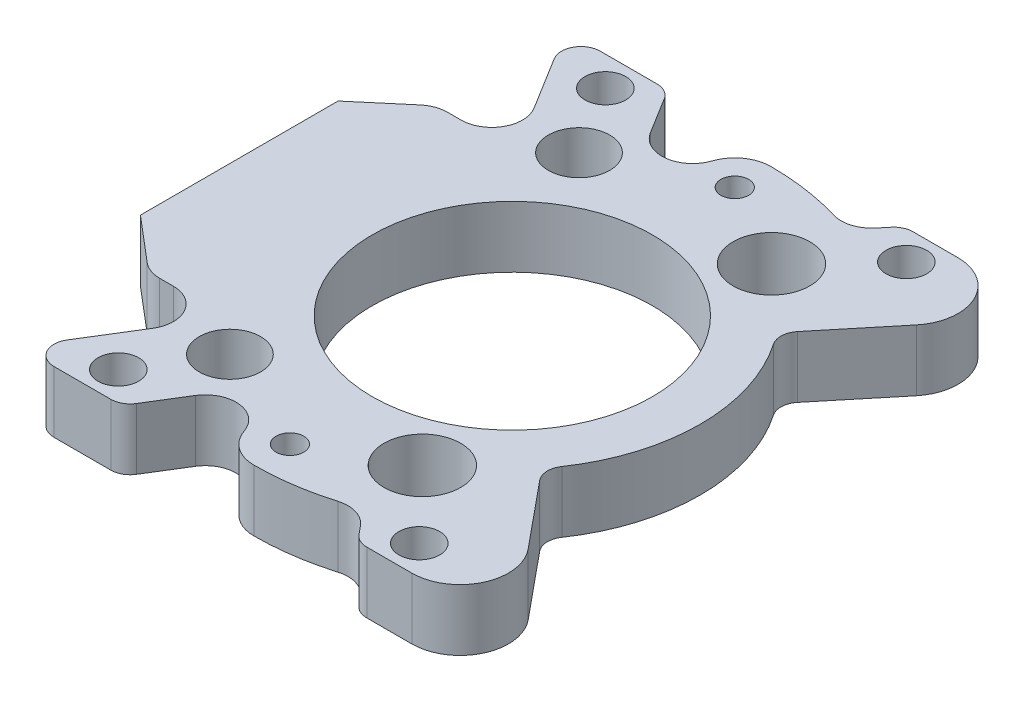
SolidWorks part; units mm, degrees
ref_plane "Front Plane" through (0, 0, 0) normal (0, 0, 1) x (1, 0, 0)
ref_plane "Top Plane" through (0, 0, 0) normal (0, 1, 0) x (1, 0, 0)
ref_plane "Right Plane" through (0, 0, 0) normal (1, 0, 0) x (0, 0, -1)
sketch "Sketch1" plane through (0, 0, 0) normal (0, 1, 0) x (1, 0, 0)
  line L0 (0, 56.515) -> (56.515, 0) construction
  line L1 (0, 0) -> (56.515, 0)
  line L2 (0, 0) -> (0, 56.515)
  line L3 (0, 56.515) -> (56.515, 56.515)
  line L4 (56.515, 0) -> (56.515, 56.515)
  line L6 (12.6873, 3.0607) -> (43.8277, 3.0607) construction
  line L7 (12.6873, 3.0607) -> (12.6873, 53.4543) construction
  line L8 (12.6873, 53.4543) -> (43.8277, 53.4543) construction
  line L9 (43.8277, 3.0607) -> (43.8277, 53.4543) construction
  line L10 (12.6873, 3.0607) -> (43.8277, 53.4543) construction
  line L11 (12.6873, 53.4543) -> (43.8277, 3.0607) construction
  circle A0 centre (43.8277, 3.0607) radius 2.1082
  circle A1 centre (12.6873, 3.0607) radius 2.1082
  circle A2 centre (12.6873, 53.4543) radius 2.1082
  circle A3 centre (43.8277, 53.4543) radius 2.1082
  circle A4 centre (28.2575, 28.2575) radius 14.5
  point P5 (28.2575, 28.2575)
  point P6 (28.2575, 28.2575)
  dimension "D5" = 4.2164
  dimension "D6" = 29
  dimension "D1" = 56.515
  dimension "D2" = 56.515
  dimension "D3" = 31.1404
  dimension "D4" = 50.3936
extrude "Boss-Extrude1" add sketch "Sketch1" along normal blind 6.35
sketch "Sketch3" plane through (0, 6.35, 0) normal (0, 1, 0) x (1, 0, 0)
  line L0 (51.5305, 0) -> (38.0741, 16.3385) construction
  line L1 (37.1401, 4.8887) -> (41.1665, 0) construction
  line L2 (0, 0) -> (56.515, 0) construction
  line L3 (43.8277, 3.0607) -> (-7.9833, 65.9682) construction
  line L4 (51.5305, 0) -> (41.1665, 0) construction
  line L5 (0, 18.6883) -> (7.198, 12.5871) construction
  line L6 (0.2175, 18.5039) -> (5.6815, 13.8725) construction
  line L7 (0, 56.515) -> (0, 0) construction
  line L8 (5.6815, 13.8725) -> (22.645, 13.8725) construction
  line L9 (22.645, 13.8725) -> (25.7282, 2.1296) construction
  line L10 (25.1261, 4.4228) -> (22.645, 13.8725) construction
  line L11 (23.0701, 12.2536) -> (15.4981, 0) construction
  line L12 (14.6663, 13.8725) -> (6.0939, 0) construction
  line L13 (12.6873, 3.0607) -> (50.1607, 63.7028) construction
  line L14 (5.6815, 13.8725) -> (22.645, 13.8725) construction
  line L15 (41.1665, 0) -> (37.9766, 3.8731)
  line L16 (23.0701, 12.2536) -> (25.1261, 4.4228)
  line L17 (23.0701, 12.2536) -> (15.4981, 0)
  line L18 (40.9306, -0.5) -> (37.821, 3.2755) construction
  line L19 (22.8825, 10.9989) -> (24.6425, 4.2958) construction
  line L20 (40.5187, 0) -> (39.2133, 1.585)
  line L21 (51.5305, 0) -> (38.0741, 16.3385) construction
  line L22 (19.0019, 4.7189) -> (16.0858, 0)
  line L23 (40.5187, 0) -> (16.0858, 0)
  line L24 (6.0939, 0) -> (14.6663, 13.8725)
  line L25 (14.6663, 13.8725) -> (5.6815, 13.8725)
  line L26 (5.6815, 13.8725) -> (0, 18.6883)
  line L27 (5.6685, 0.2628) -> (10.7762, 8.5285)
  line L28 (8.0753, 13.3725) -> (6.6627, 13.3725)
  line L29 (4.6098, 14.1255) -> (0, 18.0328)
  line L30 (5.6685, 0.2628) -> (13.7696, 13.3725) construction
  line L31 (13.7696, 13.3725) -> (5.4982, 13.3725) construction
  line L32 (5.4982, 13.3725) -> (-0.3233, 18.3068) construction
  line L33 (0, 0) -> (0, 18.0328)
  line L34 (0, 0) -> (5.5061, 0)
  line L35 (5.6685, 0.2628) -> (5.5061, 0)
  line L36 (22.8825, 10.9989) -> (15.9234, -0.2628) construction
  line L37 (52.5901, -0.5) -> (38.46, 16.6563) construction
  line L38 (52.5901, -0.5) -> (40.9306, -0.5) construction
  line L39 (56.515, 28.2575) -> (28.2575, 28.2575) construction
  line L40 (56.515, 0) -> (56.515, 56.515) construction
  line L41 (51.5305, 56.515) -> (38.0741, 40.1765) construction
  line L42 (54.6181, 53.972) -> (44.4315, 41.6037)
  line L43 (54.6181, 2.543) -> (44.4315, 14.9113)
  line L44 (54.6181, 53.972) -> (43.4402, 40.4001) construction
  line L45 (54.6181, 2.543) -> (43.4402, 16.1149) construction
  line L48 (56.515, 56.515) -> (0, 56.515) construction
  line L50 (56.515, 56.515) -> (56.515, 0)
  line L52 (0, 56.515) -> (5.5061, 56.515)
  line L53 (5.6685, 56.2522) -> (5.5061, 56.515)
  line L54 (5.6685, 56.2522) -> (10.7762, 47.9865)
  line L55 (8.0753, 43.1425) -> (6.6627, 43.1425)
  line L56 (4.6098, 42.3895) -> (0, 38.4822)
  line L57 (0, 56.515) -> (0, 38.4822)
  line L58 (40.5187, 56.515) -> (16.0858, 56.515)
  line L59 (40.5187, 56.515) -> (39.2133, 54.93)
  line L60 (19.0019, 51.7961) -> (16.0858, 56.515)
  line L61 (37.0084, 10.1975) -> (8.0753, 10.1975) construction
  line L62 (33.87, 13.8725) -> (31.3889, 4.4228) construction
  circle A0 centre (28.2575, 51.27) radius 1.435
  circle A1 centre (28.2575, 5.245) radius 1.435
  arc A2 (33.87, 13.8725) -> (33.87, 42.6425) centre (28.2575, 28.2575) ccw construction
  circle A3 centre (28.2575, 28.2575) radius 14.5 construction
  circle A4 centre (28.2575, 28.2575) radius 25 construction
  circle A5 centre (28.2575, 28.2575) radius 26.25 construction
  arc A6 (25.1261, 4.4228) -> (31.3889, 4.4228) centre (28.2575, 5.245) ccw construction
  arc A7 (7.198, 12.5871) -> (37.9766, 3.8731) centre (28.2575, 28.2575) ccw construction
  circle A8 centre (28.2575, 28.2575) radius 14.5 construction
  circle A9 centre (28.2575, 5.245) radius 1.435 construction
  circle A10 centre (28.2575, 51.27) radius 1.435 construction
  arc A11 (37.9766, 3.8731) -> (28.2575, 2.0075) centre (28.2575, 28.2575) cw
  arc A12 (25.1261, 4.4228) -> (28.2575, 2.0075) centre (28.2575, 5.245) ccw
  arc A13 (35.8601, 2.6106) -> (28.2575, 1.5075) centre (28.2575, 28.2575) cw
  arc A14 (24.7134, 4.0582) -> (28.2575, 1.5075) centre (28.2575, 5.245) ccw
  arc A15 (37.821, 3.2755) -> (28.2575, 1.5075) centre (28.2575, 28.2575) cw construction
  arc A16 (10.7762, 8.5285) -> (8.0753, 13.3725) centre (8.0753, 10.1975) ccw
  arc A17 (4.6098, 14.1255) -> (6.6627, 13.3725) centre (6.6627, 16.5475) ccw
  arc A18 (39.2133, 1.585) -> (35.8601, 2.6106) centre (36.7625, -0.4334) ccw
  arc A19 (24.7134, 4.0582) -> (19.0019, 4.7189) centre (21.7028, 3.0499) ccw
  arc A20 (38.0741, 40.1765) -> (38.0741, 16.3385) centre (28.2575, 28.2575) cw
  arc A21 (24.6425, 4.2958) -> (28.2575, 1.5075) centre (28.2575, 5.245) ccw construction
  arc A22 (44.3226, 39.2059) -> (44.3226, 17.3091) centre (28.2575, 28.2575) cw
  arc A23 (43.4402, 40.4001) -> (43.4402, 16.1149) centre (28.2575, 28.2575) cw construction
  arc A24 (44.3226, 39.2059) -> (44.4315, 41.6037) centre (45.9753, 40.3323) cw
  arc A25 (44.4315, 14.9113) -> (44.3226, 17.3091) centre (45.9753, 16.1827) cw
  arc A26 (10.7762, 47.9865) -> (8.0753, 43.1425) centre (8.0753, 46.3175) cw
  arc A27 (4.6098, 42.3895) -> (6.6627, 43.1425) centre (6.6627, 39.9675) cw
  arc A28 (39.2133, 54.93) -> (35.8601, 53.9044) centre (36.7625, 56.9484) cw
  arc A29 (35.8601, 53.9044) -> (28.2575, 55.0075) centre (28.2575, 28.2575) ccw
  arc A30 (24.7134, 52.4568) -> (28.2575, 55.0075) centre (28.2575, 51.27) cw
  arc A31 (24.7134, 52.4568) -> (19.0019, 51.7961) centre (21.7028, 53.4651) cw
  circle A32 centre (37.0084, 10.1975) radius 3.9687
  circle A33 centre (17.0974, 10.1975) radius 3.175
  circle A34 centre (17.0974, 46.3175) radius 3.175
  circle A35 centre (37.0084, 46.3175) radius 3.9688
  arc A36 (46.117, 0) -> (49.9765, 8.1787) centre (46.117, 5) ccw
  arc A38 (46.117, 56.515) -> (49.9765, 48.3363) centre (46.117, 51.515) cw
  point P60 (18.0224, 4.0851)
  point P84 (36.3745, 41.393)
  point P113 (0, 0)
  point P114 (50.6977, 49.2119)
  point P115 (56.0653, 55.7291)
  point P121 (57.9114, -1.4557)
  line M1 (0, 56.515) -> (0, 0)
  line M2 (0, 0) -> (56.515, 0)
  line M3 (56.515, 0) -> (56.515, 56.515)
  line M4 (56.515, 56.515) -> (0, 56.515)
  dimension "D1" = 50
  dimension "D4" = 29
  dimension "D11" = 3.175
  dimension "D12" = 3.175
  dimension "D8" = 3.175
  dimension "D9" = 3.175
  dimension "D14" = 2
  dimension "D15" = 2
  dimension "D16" = 7.9375
  dimension "D17" = 6.35
  dimension "D19" = 5
  dimension "D2" = 8
  dimension "D3" = 4
  dimension "D5" = 8
  dimension "D6" = 4
  dimension "D10" = 0.5
  dimension "D7" = 0.5
  dimension "D13" = 4
extrude "Cut-Extrude1" cut sketch "Sketch3" against normal through all contours A25 L43 L42 A24 A22 M2 M3 M4 | A14 A19 L22 L20 A18 A13 M2 | A17 L29 L35 L27 A16 L28 M1 M2 | L56 A27 L55 A26 L54 L53 M4 M1 | A31 A30 A29 A28 L59 L60 M4 | A33 | A32 | A35 | A34 | A0 | A1 region at (26.1526, 6.35, -1.9586) region at (51.7924, 6.35, -28.2575) region at (4.445, 6.35, -8.0938) region at (26.1526, 6.35, -54.5564) region at (4.445, 6.35, -48.4212) region at (28.2575, 6.35, -51.27) region at (28.2575, 6.35, -5.245) region at (37.0084, 6.35, -10.1975) region at (17.0974, 6.35, -10.1975) region at (17.0974, 6.35, -46.3175) region at (37.0084, 6.35, -46.3175)
fillet "Fillet1" radius 2 6 edges at (5.5061, 3.175, 0) (5.5061, 3.175, -56.515) (40.5187, 3.175, 0) (16.0858, 3.175, 0) (16.0858, 3.175, -56.515) (40.5187, 3.175, -56.515)
sketch "Sketch4" plane through (0, 6.35, 0) normal (0, 1, 0) x (1, 0, 0)
  line L17 (39.2133, 1.585) -> (39.9187, 0.7285)
  line L18 (41.4625, 0) -> (46.117, 0)
  line L19 (49.9765, 8.1787) -> (44.4315, 14.9113)
  line L20 (44.4315, 41.6037) -> (49.9765, 48.3363)
  line L21 (46.117, 56.515) -> (41.4625, 56.515)
  line L22 (39.9187, 55.7865) -> (39.2133, 54.93)
  line L23 (19.0019, 51.7961) -> (16.672, 55.5664)
  line L24 (14.9707, 56.515) -> (9.093, 56.515)
  line L25 (7.3917, 53.4636) -> (10.7762, 47.9865)
  line L26 (8.0753, 43.1425) -> (6.6627, 43.1425)
  line L27 (4.6098, 42.3895) -> (0, 38.4822)
  line L28 (0, 38.4822) -> (0, 18.0328)
  line L29 (0, 18.0328) -> (4.6098, 14.1255)
  line L30 (6.6627, 13.3725) -> (8.0753, 13.3725)
  line L31 (10.7762, 8.5285) -> (7.3917, 3.0514)
  line L32 (9.093, 0) -> (14.9707, 0)
  line L33 (16.672, 0.9486) -> (19.0019, 4.7189)
  line L34 (39.2133, 1.585) -> (39.9187, 0.7285) construction
  line L35 (41.4625, 0) -> (46.117, 0) construction
  line L36 (49.9765, 8.1787) -> (44.4315, 14.9113) construction
  line L37 (44.4315, 41.6037) -> (49.9765, 48.3363) construction
  line L38 (46.117, 56.515) -> (41.4625, 56.515) construction
  line L39 (39.9187, 55.7865) -> (39.2133, 54.93) construction
  line L40 (19.0019, 51.7961) -> (16.672, 55.5664) construction
  line L41 (14.9707, 56.515) -> (9.093, 56.515) construction
  line L42 (7.3917, 53.4636) -> (10.7762, 47.9865) construction
  line L43 (8.0753, 43.1425) -> (6.6627, 43.1425) construction
  line L44 (4.6098, 42.3895) -> (0, 38.4822) construction
  line L45 (0, 38.4822) -> (0, 18.0328) construction
  line L46 (0, 18.0328) -> (4.6098, 14.1255) construction
  line L47 (6.6627, 13.3725) -> (8.0753, 13.3725) construction
  line L48 (10.7762, 8.5285) -> (7.3917, 3.0514) construction
  line L49 (9.093, 0) -> (14.9707, 0) construction
  line L50 (16.672, 0.9486) -> (19.0019, 4.7189) construction
  circle A0 centre (12.6873, 53.4543) radius 2.1082 construction
  circle A1 centre (12.6873, 3.0607) radius 2.1082 construction
  circle A2 centre (43.8277, 3.0607) radius 2.1082 construction
  circle A3 centre (43.8277, 53.4543) radius 2.1082 construction
  circle A4 centre (12.6873, 53.4543) radius 2.1082 construction
  circle A5 centre (12.6873, 3.0607) radius 2.1082 construction
  circle A6 centre (43.8277, 3.0607) radius 2.1082 construction
  circle A7 centre (43.8277, 53.4543) radius 2.1082 construction
  circle A8 centre (43.8277, 53.4543) radius 3.625 construction
  circle A9 centre (12.6873, 53.4543) radius 3.625 construction
  circle A10 centre (43.8277, 3.0607) radius 3.625 construction
  circle A11 centre (12.6873, 3.0607) radius 3.625 construction
  arc A35 (39.9187, 0.7285) -> (41.4625, 0) centre (41.4625, 2) ccw
  arc A36 (46.117, 0) -> (49.9765, 8.1787) centre (46.117, 5) ccw
  arc A37 (44.3226, 17.3091) -> (44.4315, 14.9113) centre (45.9753, 16.1827) ccw
  arc A38 (44.3226, 17.3091) -> (44.3226, 39.2059) centre (28.2575, 28.2575) ccw
  arc A39 (44.4315, 41.6037) -> (44.3226, 39.2059) centre (45.9753, 40.3323) ccw
  arc A40 (49.9765, 48.3363) -> (46.117, 56.515) centre (46.117, 51.515) ccw
  arc A41 (41.4625, 56.515) -> (39.9187, 55.7865) centre (41.4625, 54.515) ccw
  arc A42 (35.8601, 53.9044) -> (39.2133, 54.93) centre (36.7625, 56.9484) ccw
  arc A43 (35.8601, 53.9044) -> (28.2575, 55.0075) centre (28.2575, 28.2575) ccw
  arc A44 (28.2575, 55.0075) -> (24.7134, 52.4568) centre (28.2575, 51.27) ccw
  arc A45 (19.0019, 51.7961) -> (24.7134, 52.4568) centre (21.7028, 53.4651) ccw
  arc A46 (16.672, 55.5664) -> (14.9707, 56.515) centre (14.9707, 54.515) ccw
  arc A47 (9.093, 56.515) -> (7.3917, 53.4636) centre (9.093, 54.515) ccw
  arc A48 (8.0753, 43.1425) -> (10.7762, 47.9865) centre (8.0753, 46.3175) ccw
  arc A49 (6.6627, 43.1425) -> (4.6098, 42.3895) centre (6.6627, 39.9675) ccw
  arc A50 (4.6098, 14.1255) -> (6.6627, 13.3725) centre (6.6627, 16.5475) ccw
  arc A51 (10.7762, 8.5285) -> (8.0753, 13.3725) centre (8.0753, 10.1975) ccw
  arc A52 (7.3917, 3.0514) -> (9.093, 0) centre (9.093, 2) ccw
  arc A53 (14.9707, 0) -> (16.672, 0.9486) centre (14.9707, 2) ccw
  arc A54 (24.7134, 4.0582) -> (19.0019, 4.7189) centre (21.7028, 3.0499) ccw
  arc A55 (24.7134, 4.0582) -> (28.2575, 1.5075) centre (28.2575, 5.245) ccw
  arc A56 (28.2575, 1.5075) -> (35.8601, 2.6106) centre (28.2575, 28.2575) ccw
  arc A57 (39.2133, 1.585) -> (35.8601, 2.6106) centre (36.7625, -0.4334) ccw
  arc A58 (39.9187, 0.7285) -> (41.4625, 0) centre (41.4625, 2) ccw construction
  arc A59 (46.117, 0) -> (49.9765, 8.1787) centre (46.117, 5) ccw construction
  arc A60 (44.3226, 17.3091) -> (44.4315, 14.9113) centre (45.9753, 16.1827) ccw construction
  arc A61 (44.3226, 17.3091) -> (44.3226, 39.2059) centre (28.2575, 28.2575) ccw construction
  arc A62 (44.4315, 41.6037) -> (44.3226, 39.2059) centre (45.9753, 40.3323) ccw construction
  arc A63 (49.9765, 48.3363) -> (46.117, 56.515) centre (46.117, 51.515) ccw construction
  arc A64 (41.4625, 56.515) -> (39.9187, 55.7865) centre (41.4625, 54.515) ccw construction
  arc A65 (35.8601, 53.9044) -> (39.2133, 54.93) centre (36.7625, 56.9484) ccw construction
  arc A66 (35.8601, 53.9044) -> (28.2575, 55.0075) centre (28.2575, 28.2575) ccw construction
  arc A67 (28.2575, 55.0075) -> (24.7134, 52.4568) centre (28.2575, 51.27) ccw construction
  arc A68 (19.0019, 51.7961) -> (24.7134, 52.4568) centre (21.7028, 53.4651) ccw construction
  arc A69 (16.672, 55.5664) -> (14.9707, 56.515) centre (14.9707, 54.515) ccw construction
  arc A70 (9.093, 56.515) -> (7.3917, 53.4636) centre (9.093, 54.515) ccw construction
  arc A71 (8.0753, 43.1425) -> (10.7762, 47.9865) centre (8.0753, 46.3175) ccw construction
  arc A72 (6.6627, 43.1425) -> (4.6098, 42.3895) centre (6.6627, 39.9675) ccw construction
  arc A73 (4.6098, 14.1255) -> (6.6627, 13.3725) centre (6.6627, 16.5475) ccw construction
  arc A74 (10.7762, 8.5285) -> (8.0753, 13.3725) centre (8.0753, 10.1975) ccw construction
  arc A75 (7.3917, 3.0514) -> (9.093, 0) centre (9.093, 2) ccw construction
  arc A76 (14.9707, 0) -> (16.672, 0.9486) centre (14.9707, 2) ccw construction
  arc A77 (24.7134, 4.0582) -> (19.0019, 4.7189) centre (21.7028, 3.0499) ccw construction
  arc A78 (24.7134, 4.0582) -> (28.2575, 1.5075) centre (28.2575, 5.245) ccw construction
  arc A79 (28.2575, 1.5075) -> (35.8601, 2.6106) centre (28.2575, 28.2575) ccw construction
  arc A80 (39.2133, 1.585) -> (35.8601, 2.6106) centre (36.7625, -0.4334) ccw construction
  dimension "D1" = 7.25
  dimension "D2" = 0
equation "\"D3@Sketch3\"=\"D2@Sketch3\"/2"
